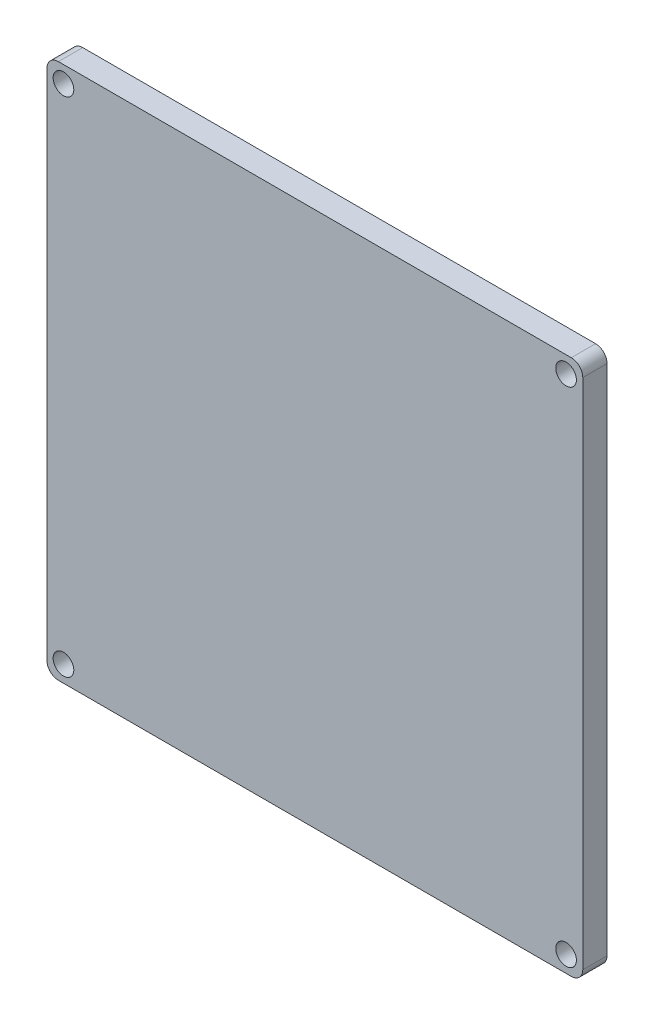
SolidWorks part; units mm, degrees
ref_plane "Front Plane" through (0, 0, 0) normal (0, 0, 1) x (1, 0, 0)
ref_plane "Top Plane" through (0, 0, 0) normal (0, 1, 0) x (1, 0, 0)
ref_plane "Right Plane" through (0, 0, 0) normal (1, 0, 0) x (0, 0, -1)
sketch "Sketch1" plane through (0, 0, 0) normal (0, 0, 1) x (1, 0, 0)
  line L1 (-35, 35) -> (35, 35)
  line L2 (-35, 35) -> (-35, -35)
  line L3 (-35, -35) -> (35, -35)
  line L4 (35, 35) -> (35, -35)
  line L5 (-35, 35) -> (35, -35) construction
  line L6 (-35, -35) -> (35, 35) construction
  circle A0 centre (-32.84, 32.82) radius 1.35
  circle A2 centre (-32.84, -32.84) radius 1.35
  circle A3 centre (32.82, -32.84) radius 1.35
  circle A4 centre (32.82, 32.82) radius 1.35
  point P0 (0, 0)
  point P14 (0, 0)
  point P15 (0, 0)
  point P16 (0, 0)
  dimension "D5" = 2.7
  dimension "D7" = 2.7
  dimension "D9" = 2.7
  dimension "D12" = 2.7
  dimension "D1" = 70
  dimension "D2" = 70
  dimension "D3" = 2.16
  dimension "D4" = 2.16
  dimension "D6" = 65.66
  dimension "D8" = 65.66
  dimension "D10" = 65.66
  dimension "D11" = 65.66
extrude "Boss-Extrude1" add sketch "Sketch1" along normal blind 3.175
fillet "Fillet1" radius 1.5 4 edges at (35, 35, 1.5875) (35, -35, 1.5875) (-35, -35, 1.5875) (-35, 35, 1.5875)
